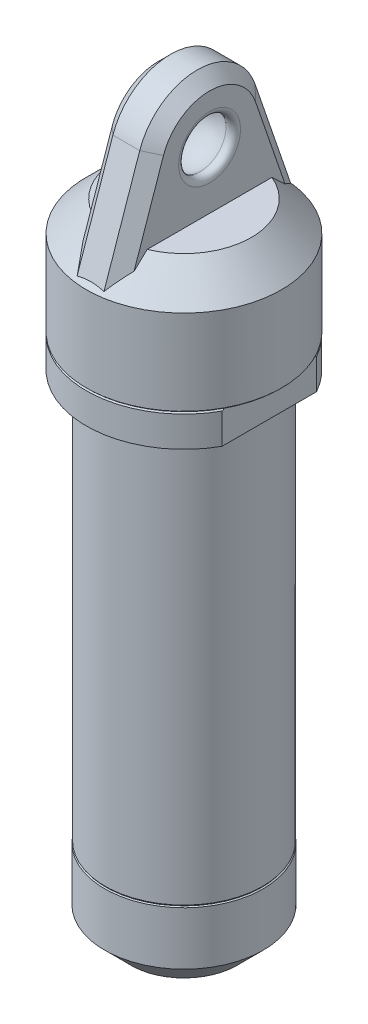
SolidWorks part; units mm, degrees
ref_plane "Front Plane" through (0, 0, 0) normal (0, 0, 1) x (1, 0, 0)
ref_plane "Top Plane" through (0, 0, 0) normal (0, 1, 0) x (1, 0, 0)
ref_plane "Right Plane" through (0, 0, 0) normal (1, 0, 0) x (0, 0, -1)
sketch "Sketch1" plane through (0, 0, 0) normal (1, 0, 0) x (0, 0, -1)
  line L0 (0, 0) -> (5.5251, 0)
  line L1 (5.5251, 0) -> (8, -2.4749)
  line L2 (8, -2.4749) -> (8, -9.45)
  line L5 (8, -9.65) -> (8, -12.15)
  line L6 (8, -12.15) -> (6.465, -12.15)
  line L7 (6.465, -12.15) -> (6.465, -45.6)
  line L8 (6.465, -45.6) -> (6.4, -45.7)
  line L9 (6.4, -45.7) -> (6.5, -45.765)
  line L10 (6.5, -45.765) -> (6.5, -50.1287)
  line L12 (4.3787, -52.25) -> (1.5, -52.25)
  line L13 (1.5, -52.25) -> (1.5, -10)
  line L14 (1.5, -10) -> (0, -10)
  line L15 (0, -10) -> (0, 0)
  line L16 (8, -9.65) -> (7.9, -9.55)
  line L17 (7.9, -9.55) -> (8, -9.45)
  line L19 (4.3787, -52.25) -> (6.5, -50.1287)
  dimension "D1" = 1.5
  dimension "D2" = 6.465
  dimension "D3" = 6.5
  dimension "D4" = 45.7
  dimension "D5" = 8
  dimension "D6" = 12.15
  dimension "D7" = 2.5
  dimension "D8" = 8
  dimension "D9" = 45
  dimension "D10" = 0.1
  dimension "D11" = 45
  dimension "D12" = 3.5
  dimension "D13" = 52.25
  dimension "D14" = 45
  dimension "D15" = 3
  dimension "D16" = 0.1
  dimension "D17" = 10
revolve "Revolve1" add sketch "Sketch1" angle 360 about L15
sketch "Sketch2" plane through (0, 0, 0) normal (1, 0, 0) x (0, 0, -1)
  line L0 (-7.75, -2.4749) -> (-4.729, 6.3237)
  line L1 (4.729, 6.3237) -> (7.75, -2.4749)
  line L2 (-7.75, -2.4749) -> (7.75, -2.4749)
  line L3 (5.5251, 0) -> (-5.5251, 0) construction
  line L4 (8, -2.4749) -> (-8, -2.4749) construction
  arc A0 (-4.729, 6.3237) -> (4.729, 6.3237) centre (0, 4.7) cw
  point P7 (0, 9.7)
  dimension "D1" = 5
  dimension "D2" = 9.7
  dimension "D3" = 0.25
extrude "Boss-Extrude1" add sketch "Sketch2" along normal mid plane 4.2
chamfer "Chamfer1" distance 1 angle 45 6 edges at (-2.1, 1.9244, 6.2395) (2.1, 1.9244, 6.2395) (-2.1, 1.9244, -6.2395) (-2.1, 9.7, 0) (2.1, 1.9244, -6.2395) (2.1, 9.7, 0)
sketch "Sketch3" plane through (0, -12.15, 0) normal (0, -1, 0) x (1, 0, 0)
  line L0 (-7, 3.873) -> (-7, -3.873)
  line L1 (0, -8.8) -> (0, 8.8) construction
  line L2 (7, 3.873) -> (7, -3.873)
  arc A0 (-7, 3.873) -> (-7, -3.873) centre (0, 0) ccw
  circle A1 centre (0, 0) radius 8
  arc A2 (7, -3.873) -> (7, 3.873) centre (0, 0) ccw
  dimension "D2" = 14
  dimension "D1" = 0
ref_plane "Plane1" through (0, -9.55, 0) normal (0, 1, 0) x (1, 0, 0)
extrude "Cut-Extrude1" cut sketch "Sketch3" against normal up to surface (2.6 mm away) up to plane "Plane1"
sketch "Sketch4" plane through (0, 0, 0) normal (1, 0, 0) x (0, 0, -1)
  line L0 (0, 7.2) -> (0, 2.2) construction
  line L1 (-4.3787, -52.25) -> (4.3787, -52.25) construction
  circle A0 centre (0, 4.7) radius 2.5
  arc A1 (3.7832, 5.999) -> (-3.7832, 5.999) centre (0, 4.7) ccw construction
  dimension "D1" = 5
revolve "Cut-Revolve3" cut sketch "Sketch4" angle 360 about L0 region at (0, 4.7, 1.061)
fillet "Fillet1" radius 0.5 2 edges at (2.1, 4.7, 1.3565) (-2.1, 4.7, 1.3565)
